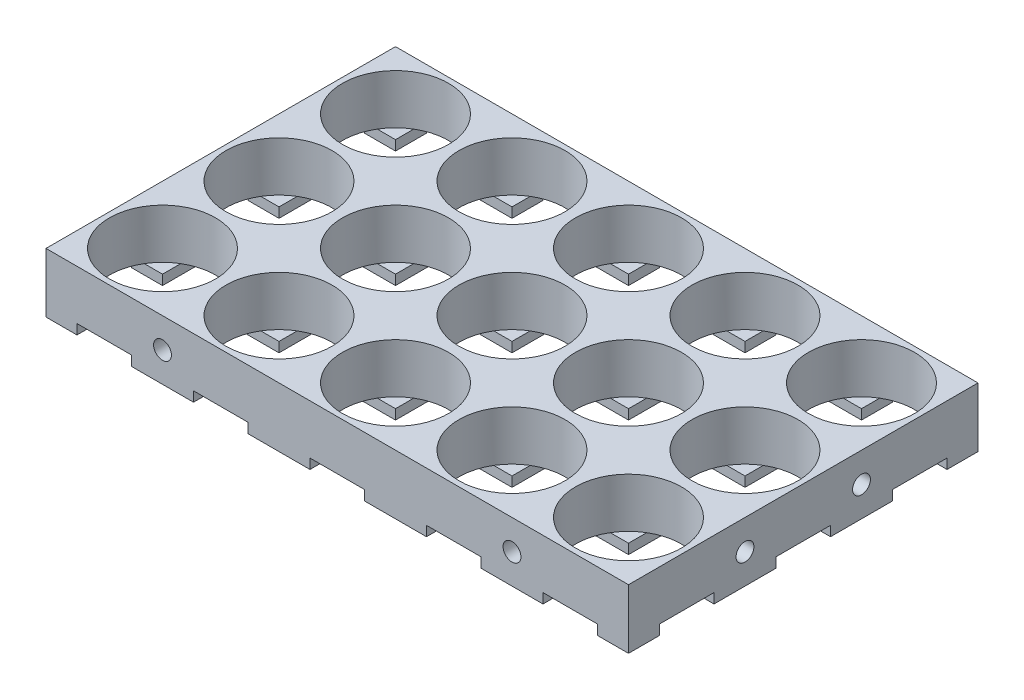
SolidWorks part; units mm, degrees
ref_plane "Front Plane" through (0, 0, 0) normal (0, 0, 1) x (1, 0, 0)
ref_plane "Top Plane" through (0, 0, 0) normal (0, 1, 0) x (1, 0, 0)
ref_plane "Right Plane" through (0, 0, 0) normal (1, 0, 0) x (0, 0, -1)
sketch "Sketch1" plane through (0, 0, 0) normal (0, 1, 0) x (1, 0, 0)
  line L1 (-11.75, -11.75) -> (11.75, -11.75)
  line L2 (-11.75, -11.75) -> (-11.75, 11.75)
  line L3 (-11.75, 11.75) -> (11.75, 11.75)
  line L4 (11.75, -11.75) -> (11.75, 11.75)
  line L5 (-11.75, -11.75) -> (11.75, 11.75) construction
  line L6 (-11.75, 11.75) -> (11.75, -11.75) construction
  circle A0 centre (0, 0) radius 10.7
  dimension "D1" = 21.4
  dimension "D2" = 23.5
extrude "Boss-Extrude1" add sketch "Sketch1" along normal blind 10
sketch "Sketch4" plane through (0, 0, 0) normal (0, -1, 0) x (1, 0, 0)
  line L1 (-11.75, 11.75) -> (-5.5, 11.75)
  line L2 (-11.75, 11.75) -> (-11.75, 5.5)
  line L3 (-11.75, 5.5) -> (-5.5, 5.5)
  line L4 (-5.5, 11.75) -> (-5.5, 5.5)
  line L5 (11.75, 11.75) -> (5.5, 11.75)
  line L6 (11.75, 11.75) -> (11.75, 5.5)
  line L7 (11.75, 5.5) -> (5.5, 5.5)
  line L8 (5.5, 11.75) -> (5.5, 5.5)
  line L9 (11.75, -11.75) -> (5.5, -11.75)
  line L10 (11.75, -11.75) -> (11.75, -5.5)
  line L11 (11.75, -5.5) -> (5.5, -5.5)
  line L12 (5.5, -11.75) -> (5.5, -5.5)
  line L13 (-11.75, -11.75) -> (-5.5, -11.75)
  line L14 (-11.75, -11.75) -> (-11.75, -5.5)
  line L15 (-11.75, -5.5) -> (-5.5, -5.5)
  line L16 (-5.5, -11.75) -> (-5.5, -5.5)
  dimension "D1" = 11
extrude "Boss-Extrude2" add sketch "Sketch4" along normal blind 2
pattern_linear "LPattern2" count 5 spacing 23.5 along (1, 0, 0) count 3 spacing 23.5 along (0, 0, 1) of bodies 117
combine bodies "Combine2" operation type add bodies to combine 118 119 120 121 126 125 124 123 122 127 128 129 130 131 117
sketch "Sketch6" plane through (-11.75, 0, 0) normal (-1, 0, 0) x (0, 0, 1)
  line L0 (11.75, -2) -> (11.75, 10) construction
  line L1 (18, -2) -> (5.5, -2) construction
  line L2 (-11.75, 10) -> (58.75, 10) construction
  line L3 (35.25, -2) -> (35.25, 10) construction
  line L4 (41.5, -2) -> (29, -2) construction
  circle A0 centre (11.75, 4) radius 1.8
  circle A1 centre (35.25, 4) radius 1.8
  dimension "D1" = 3.6
extrude "Cut-Extrude1" cut sketch "Sketch6" against normal blind 6
sketch "Sketch7" plane through (0, 0, -11.75) normal (0, 0, -1) x (-1, 0, 0)
  line L0 (-82.25, -2) -> (-82.25, 10) construction
  line L1 (-76, -2) -> (-88.5, -2) construction
  line L2 (-105.75, 10) -> (11.75, 10) construction
  line L3 (-11.75, -2) -> (-11.75, 10) construction
  line L4 (-5.5, -2) -> (-18, -2) construction
  circle A0 centre (-82.25, 4) radius 1.8
  circle A1 centre (-11.75, 4) radius 1.8
  dimension "D1" = 3.6
extrude "Cut-Extrude2" cut sketch "Sketch7" against normal blind 6
sketch "Sketch8" plane through (105.75, 0, 0) normal (1, 0, 0) x (0, 0, -1)
  line L0 (-35.25, -2) -> (-35.25, 10) construction
  line L1 (-29, -2) -> (-41.5, -2) construction
  line L2 (-58.75, 10) -> (11.75, 10) construction
  line L3 (-11.75, -2) -> (-11.75, 10) construction
  line L4 (-5.5, -2) -> (-18, -2) construction
  circle A0 centre (-35.25, 4) radius 1.8
  circle A1 centre (-11.75, 4) radius 1.8
  dimension "D1" = 3.6
extrude "Cut-Extrude3" cut sketch "Sketch8" against normal blind 6
sketch "Sketch9" plane through (0, 0, 58.75) normal (0, 0, 1) x (1, 0, 0)
  line L0 (11.75, -2) -> (11.75, 10) construction
  line L1 (18, -2) -> (5.5, -2) construction
  line L2 (-11.75, 10) -> (105.75, 10) construction
  line L3 (82.25, -2) -> (82.25, 10) construction
  line L4 (88.5, -2) -> (76, -2) construction
  circle A0 centre (11.75, 4) radius 1.8
  circle A1 centre (82.25, 4) radius 1.8
  dimension "D1" = 3.6
extrude "Cut-Extrude4" cut sketch "Sketch9" against normal blind 6
